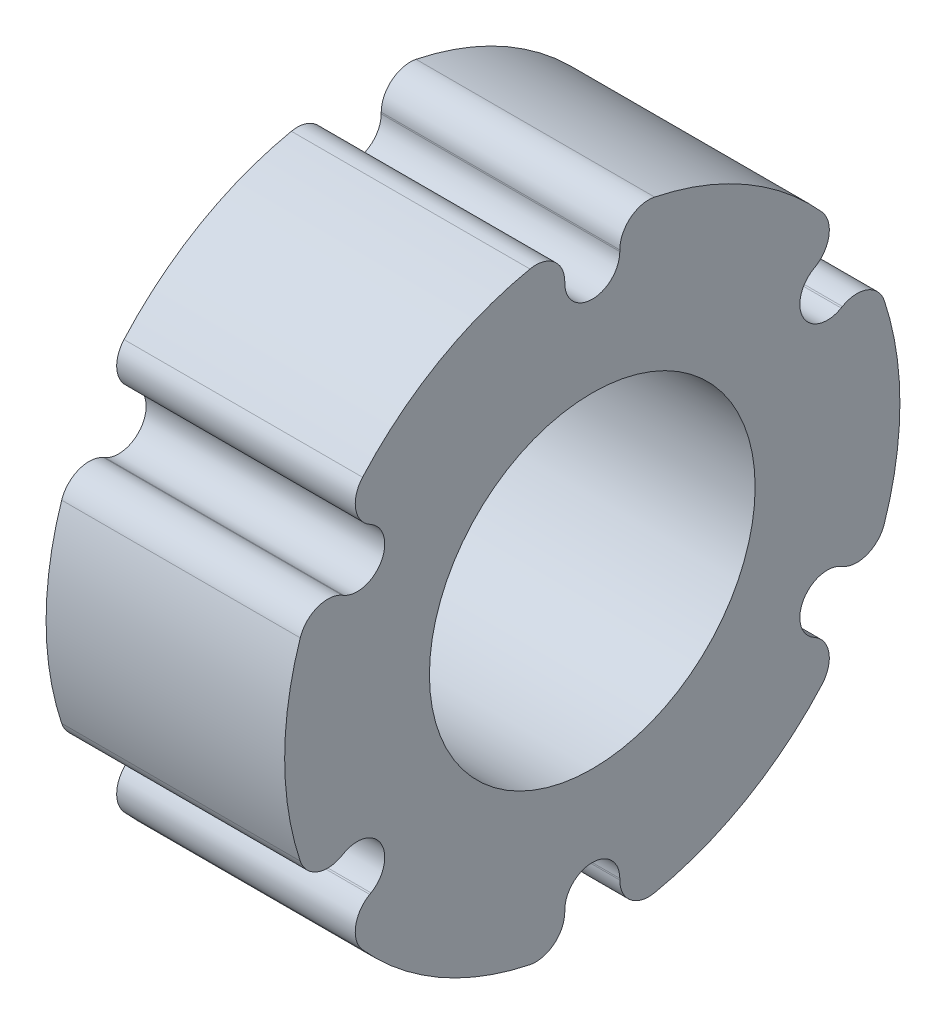
SolidWorks part; units mm, degrees
material "PET"
ref_plane "Front" through (0, 0, 0) normal (0, 0, 1) x (1, 0, 0)
ref_plane "Top" through (0, 0, 0) normal (0, 1, 0) x (1, 0, 0)
ref_plane "Right" through (0, 0, 0) normal (1, 0, 0) x (0, 0, -1)
sketch "Sketch1" plane through (0, 0, 0) normal (1, 0, 0) x (0, 0, -1)
  line L0 (-2.413, 23.8125) -> (-2.413, 23.9405)
  line L1 (2.413, 23.8125) -> (2.413, 23.9405)
  line L2 (19.4157, 13.996) -> (19.5266, 14.06)
  line L3 (21.8287, 9.8165) -> (21.9396, 9.8805)
  line L4 (21.8287, -9.8165) -> (21.9396, -9.8805)
  line L5 (19.4157, -13.996) -> (19.5266, -14.06)
  line L6 (2.413, -23.8125) -> (2.413, -23.9405)
  line L7 (-2.413, -23.8125) -> (-2.413, -23.9405)
  line L8 (-19.4157, -13.996) -> (-19.5266, -14.06)
  line L9 (-21.8287, -9.8165) -> (-21.9396, -9.8805)
  line L10 (-21.8287, 9.8165) -> (-21.9396, 9.8805)
  line L11 (-19.4157, 13.996) -> (-19.5266, 14.06)
  arc A0 (-5.4676, 26.4278) -> (-20.1534, 17.949) centre (0, 0) ccw
  circle A1 centre (0, 0) radius 23.8125 construction
  arc A2 (-2.413, 23.8125) -> (2.413, 23.8125) centre (0, 23.8125) ccw
  arc A3 (-2.413, 23.9405) -> (-5.4676, 26.4278) centre (-4.953, 23.9405) ccw
  arc A4 (2.413, 23.9405) -> (5.4676, 26.4278) centre (4.953, 23.9405) cw
  arc A5 (19.4157, 13.996) -> (21.8287, 9.8165) centre (20.6222, 11.9062) ccw
  arc A6 (19.5266, 14.06) -> (20.1534, 17.949) centre (18.2566, 16.2597) ccw
  arc A7 (21.9396, 9.8805) -> (25.621, 8.4788) centre (23.2096, 7.6808) cw
  arc A8 (21.8287, -9.8165) -> (19.4157, -13.996) centre (20.6222, -11.9063) ccw
  arc A9 (21.9396, -9.8805) -> (25.621, -8.4788) centre (23.2096, -7.6808) ccw
  arc A10 (19.5266, -14.06) -> (20.1534, -17.949) centre (18.2566, -16.2597) cw
  arc A11 (2.413, -23.8125) -> (-2.413, -23.8125) centre (0, -23.8125) ccw
  arc A12 (2.413, -23.9405) -> (5.4676, -26.4278) centre (4.953, -23.9405) ccw
  arc A13 (-2.413, -23.9405) -> (-5.4676, -26.4278) centre (-4.953, -23.9405) cw
  arc A14 (-19.4157, -13.996) -> (-21.8287, -9.8165) centre (-20.6222, -11.9062) ccw
  arc A15 (-19.5266, -14.06) -> (-20.1534, -17.949) centre (-18.2566, -16.2597) ccw
  arc A16 (-21.9396, -9.8805) -> (-25.621, -8.4788) centre (-23.2096, -7.6808) cw
  arc A17 (-21.8287, 9.8165) -> (-19.4157, 13.996) centre (-20.6222, 11.9063) ccw
  arc A18 (-21.9396, 9.8805) -> (-25.621, 8.4788) centre (-23.2096, 7.6808) ccw
  arc A19 (-19.5266, 14.06) -> (-20.1534, 17.949) centre (-18.2566, 16.2597) cw
  arc A20 (-25.621, 8.4788) -> (-25.621, -8.4788) centre (0, 0) ccw
  arc A21 (-20.1534, -17.949) -> (-5.4676, -26.4278) centre (0, 0) ccw
  arc A22 (20.1534, 17.949) -> (5.4676, 26.4278) centre (0, 0) ccw
  arc A23 (25.621, -8.4788) -> (25.621, 8.4788) centre (0, 0) ccw
  arc A24 (5.4676, -26.4278) -> (20.1534, -17.949) centre (0, 0) ccw
  circle A25 centre (0, 0) radius 14.2875
  point P59 (0, 0)
  dimension "D1" = 47.625
  dimension "D2" = 4.826
  dimension "D3" = 2.54
  dimension "D4" = 53.975
  dimension "D6" = 28.575
  dimension "D5" = 6
extrude "Boss-Extrude1" add sketch "Sketch1" along normal blind 20.9296
